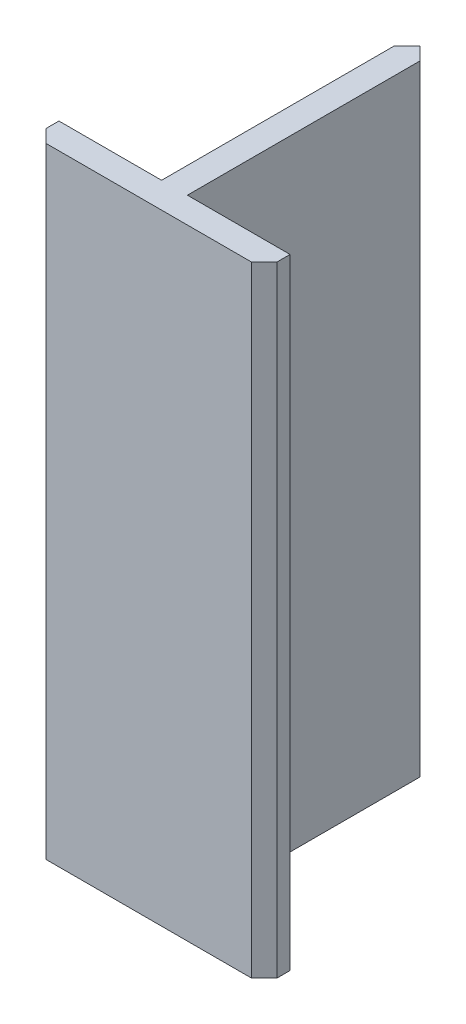
SolidWorks part; units mm, degrees
ref_plane "Front Plane" through (0, 0, 0) normal (0, 0, 1) x (1, 0, 0)
ref_plane "Top Plane" through (0, 0, 0) normal (0, 1, 0) x (1, 0, 0)
ref_plane "Right Plane" through (0, 0, 0) normal (1, 0, 0) x (0, 0, -1)
sketch "Sketch2" plane through (0, 0, 0) normal (0, 1, 0) x (1, 0, 0)
  line L0 (-11.3592, 0) -> (11.3592, 0)
  line L1 (0, 0) -> (0, 25.4)
  circle A0 centre (0, 10.16) radius 15.24 construction
  circle A1 centre (0, 10.16) radius 16.51 construction
  point P4 (0, 0)
  dimension "D1" = 1.27
  dimension "D2" = 33.02
  dimension "D3" = 25.4
extrude "Extrude-Thin1" add sketch "Sketch2" along normal mid plane 60.96 thin thin type mid plane wall 2.54
combine bodies "Combine1" operation type add bodies to combine 102 101
chamfer "Chamfer1" distance 1.27 angle 45 4 edges at (-11.3592, 0, 1.27) (11.3592, 0, 1.27) (1.27, 0, -25.4) (-1.27, 0, -25.4)
sketch "Sketch3" plane through (0, 30.48, 0) normal (0, 1, 0) x (1, 0, 0)
  circle A0 centre (0, 10.3607) radius 16.51 construction
  dimension "D1" = 33.02
